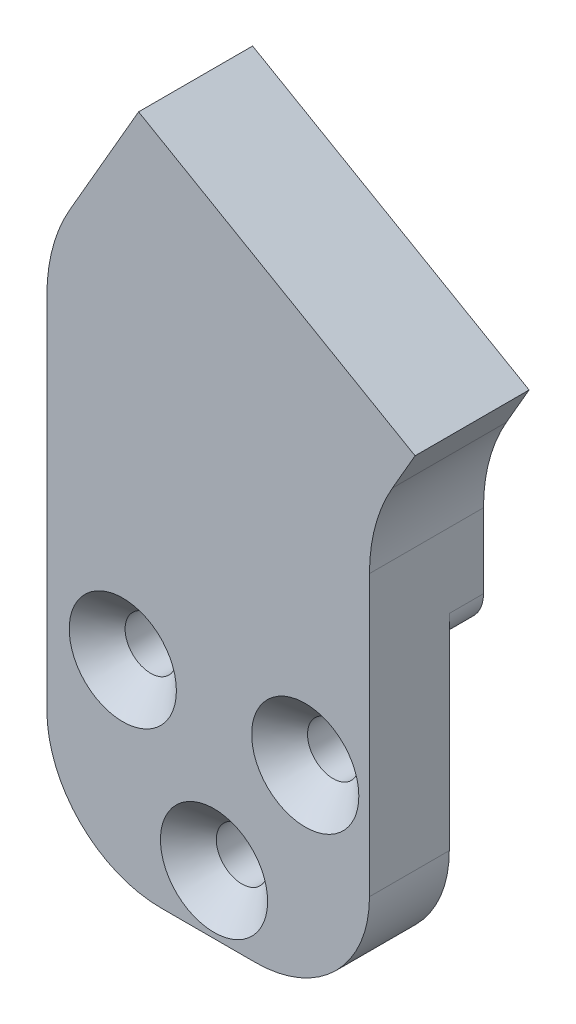
SolidWorks part; units mm, degrees
ref_plane "Front Plane" through (0, 0, 0) normal (0, 0, 1) x (1, 0, 0)
ref_plane "Top Plane" through (0, 0, 0) normal (0, 1, 0) x (1, 0, 0)
ref_plane "Right Plane" through (0, 0, 0) normal (1, 0, 0) x (0, 0, -1)
sketch "Sketch1" plane through (0, 0, 0) normal (0, 0, 1) x (1, 0, 0)
  line L5 (-14.6579, 119.617) -> (13.6331, 119.617)
  line L12 (13.6331, 119.617) -> (13.6331, 139.617)
  line L15 (-14.6579, 119.617) -> (-14.6579, 139.617)
  line L18 (-14.6579, 139.617) -> (-14.6579, 158.1769)
  line L20 (13.6331, 158.1769) -> (13.6331, 139.617)
  line L21 (-14.6579, 158.1769) -> (-14.6579, 165.1755)
  line L22 (-10.6157, 172.1769) -> (-14.6579, 165.1755)
  line L23 (-6.6157, 179.1051) -> (-10.6157, 172.1769)
  line L24 (17.6331, 165.1051) -> (13.6331, 158.1769)
  line L25 (-6.6157, 179.1051) -> (17.6331, 165.1051)
extrude "Boss-Extrude1" add sketch "Sketch1" along normal blind 9 and the other way blind 1
sketch "Sketch3" plane through (0, 0, -1) normal (0, 0, -1) x (-1, 0, 0)
  line L16 (-15, 144.2481) -> (-15, 114.7859)
  line L17 (-15, 114.7859) -> (15, 114.7859)
  line L18 (15, 114.7859) -> (15, 144.2481)
  arc A2 (15, 144.2481) -> (-15, 144.2481) centre (0, -5) ccw
extrude "Cut-Extrude1" cut sketch "Sketch3" against normal blind 3
sketch "Sketch7" plane through (0, 0, 9) normal (0, 0, -1) x (-1, 0, 0)
  line L2 (0, 124.7859) -> (0, 136.7859)
  line L3 (0, 136.7859) -> (8, 136.7859)
  line L4 (0, 136.7859) -> (-8, 136.7859)
  circle A0 centre (8, 136.7859) radius 2
  circle A1 centre (0, 124.7859) radius 2
  circle A2 centre (-8, 136.7859) radius 2
hole_wizard "CSK for M4 Countersunk Flat Head Screw2" positions "Sketch11" profile "Sketch10" countersink size "M4" standard "ISO" end condition through all
sketch "Sketch11" plane through (0, 0, 9) normal (0, 0, 1) x (1, 0, 0)
  point P0 (0, 0)
  point P1 (8, 136.7859)
  point P4 (-8, 136.7859)
  point P7 (0, 124.7859)
sketch "Sketch10" plane through (0, 0, 9) normal (1, 0, 0) x (0, -1, 0)
  line L0 (0, 0) -> (0, 10)
  line L1 (0, 10) -> (2.25, 10)
  line L2 (2.25, 10) -> (2.25, 2.45)
  line L3 (2.25, 2.45) -> (4.7, 0)
  line L5 (4.7, 0) -> (0, 0)
  line L6 (-2.25, 2.45) -> (-4.7, 0) construction
  line L11 (0, -6.35) -> (0, 107.95) construction
  dimension "Thru Hole Dia." = 4.5
  dimension "Thru Hole Depth" = 10
  dimension "Near C'Sink Dia." = 9.4
  dimension "Near C'Sink Angle" = 90
fillet "Fillet1" radius 15 2 edges at (13.6331, 158.1769, 4) (-14.6579, 165.1755, 4)
fillet "Fillet2" radius 10 2 edges at (-14.6579, 119.617, 5.5) (13.6331, 119.617, 5.5)
fillet "Fillet3" radius 3 2 edges at (13.6331, 144.3792, 0.5) (-14.6579, 144.2821, 0.5)
